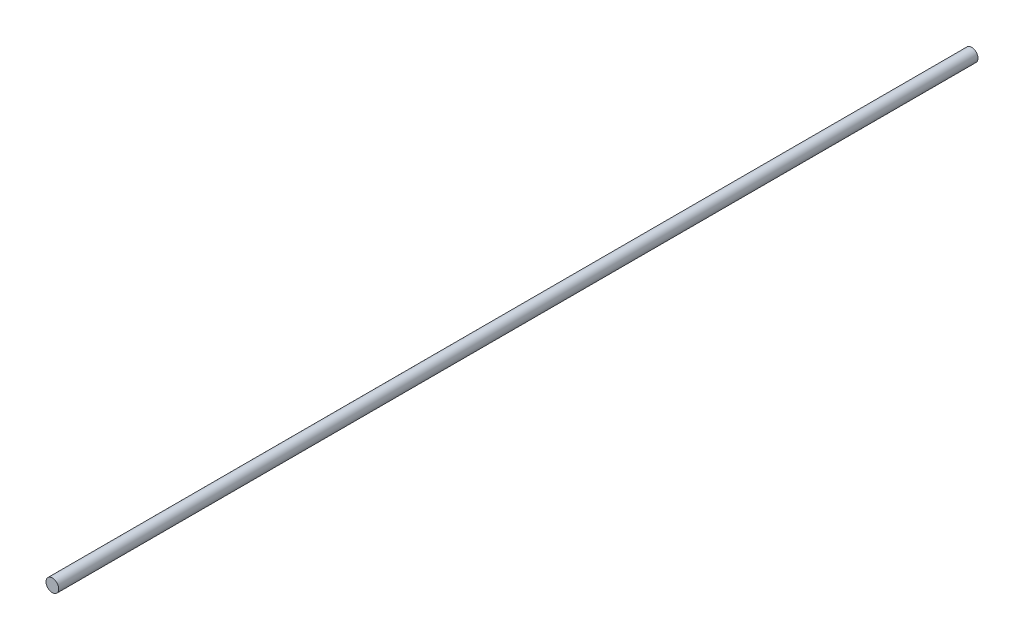
SolidWorks part; units mm, degrees
ref_plane "Front Plane" through (0, 0, 0) normal (0, 0, 1) x (1, 0, 0)
ref_plane "Top Plane" through (0, 0, 0) normal (0, 1, 0) x (1, 0, 0)
ref_plane "Right Plane" through (0, 0, 0) normal (1, 0, 0) x (0, 0, -1)
sketch "Sketch1" plane through (0, 0, 0) normal (0, 0, 1) x (1, 0, 0)
  circle A0 centre (0, 0) radius 6.35
  dimension "D1" = 12.7
extrude "Boss-Extrude1" add sketch "Sketch1" along normal mid plane 914.4
